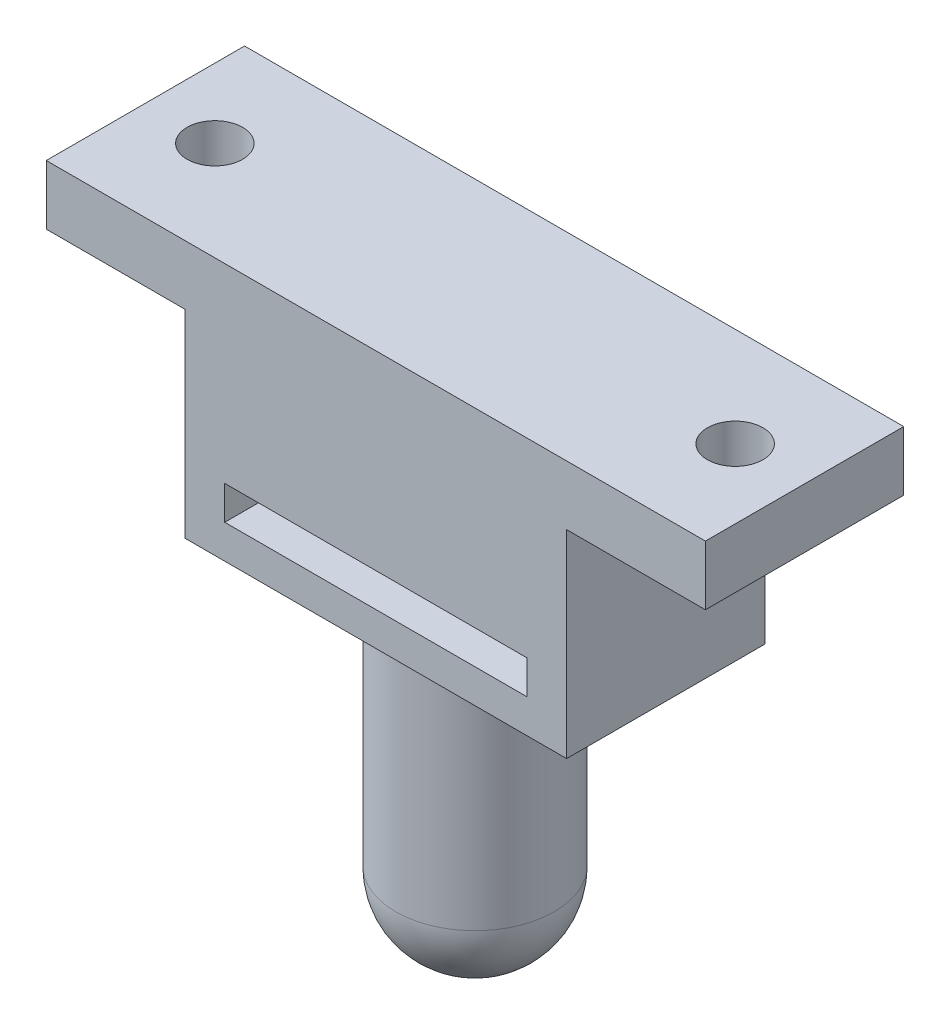
SolidWorks part; units mm, degrees
ref_plane "Front Plane" through (0, 0, 0) normal (0, 0, 1) x (1, 0, 0)
ref_plane "Top Plane" through (0, 0, 0) normal (0, 1, 0) x (1, 0, 0)
ref_plane "Right Plane" through (0, 0, 0) normal (1, 0, 0) x (0, 0, -1)
sketch "Sketch1" plane through (0, 0, 0) normal (0, 1, 0) x (1, 0, 0)
  line L1 (-9.62, -5) -> (9.62, -5)
  line L2 (-9.62, -5) -> (-9.62, 5)
  line L3 (-9.62, 5) -> (9.62, 5)
  line L4 (9.62, -5) -> (9.62, 5)
  line L5 (-9.62, -5) -> (9.62, 5) construction
  line L6 (-9.62, 5) -> (9.62, -5) construction
  line L7 (-9.62, 5) -> (-16.62, 5)
  line L8 (-9.62, 5) -> (-9.62, -5)
  line L9 (-9.62, -5) -> (-16.62, -5)
  line L10 (-16.62, 5) -> (-16.62, -5)
  line L11 (9.62, 5) -> (16.62, 5)
  line L12 (9.62, 5) -> (9.62, -5)
  line L13 (9.62, -5) -> (16.62, -5)
  line L14 (16.62, 5) -> (16.62, -5)
  point P0 (0, 0)
  dimension "D1" = 19.24
  dimension "D2" = 10
  dimension "D3" = 7
extrude "Boss-Extrude1" add sketch "Sketch1" against normal blind 3 contours L7 L10 L9 L2 | L14 L11 L4 L13 region at (-13.12, 0, 0) region at (13.12, 0, 0)
extrude "Boss-Extrude2" add sketch "Sketch1<4>" against normal blind 13 contours L1 L4 L3 L2 region at (0, 0, 0)
sketch "Sketch1<4>" plane through (0, 0, 0) normal (0, 1, 0) x (1, 0, 0) same geometry as "Sketch1"
sketch "Sketch2" plane through (0, 0, 5) normal (0, 0, 1) x (1, 0, 0)
  line L0 (0, -55) -> (0, 55) construction
  line L1 (-7.62, -11.3) -> (7.62, -11.3)
  line L2 (-7.62, -11.3) -> (-7.62, -9.6)
  line L3 (-7.62, -9.6) -> (7.62, -9.6)
  line L4 (7.62, -11.3) -> (7.62, -9.6)
  line L5 (-7.62, -11.3) -> (7.62, -9.6) construction
  line L6 (-7.62, -9.6) -> (7.62, -11.3) construction
  line L7 (55, 0) -> (-55, 0) construction
  point P0 (0, -10.45)
  dimension "D1" = 9.6
  dimension "D2" = 1.7
  dimension "D3" = 15.24
extrude "Cut-Extrude1" cut sketch "Sketch2" against normal blind 14
sketch "Sketch3" plane through (0, -13, 0) normal (0, -1, 0) x (1, 0, 0)
  circle A0 centre (0, 0) radius 4
  dimension "D1" = 8
extrude "Boss-Extrude3" add sketch "Sketch3" along normal blind 16
fillet "Fillet1" radius 4 1 edges at (0, -29, -4)
sketch "Sketch4" plane through (0, 0, 0) normal (0, 1, 0) x (1, 0, 0)
  line L0 (-7.15, 0) -> (7.15, 0) construction
  line L1 (-16.62, 5) -> (-16.62, -5) construction
  line L2 (16.62, 5) -> (16.62, -5) construction
  line L4 (-15.62, 1.4434) -> (-15.62, -1.4434)
  line L5 (-15.62, -1.4434) -> (-13.12, -2.8868)
  line L6 (-13.12, -2.8868) -> (-10.62, -1.4434)
  line L7 (-10.62, -1.4434) -> (-10.62, 1.4434)
  line L8 (-10.62, 1.4434) -> (-13.12, 2.8868)
  line L9 (-13.12, 2.8868) -> (-15.62, 1.4434)
  line L10 (10.62, 1.4434) -> (10.62, -1.4434)
  line L11 (10.62, -1.4434) -> (13.12, -2.8868)
  line L12 (13.12, -2.8868) -> (15.62, -1.4434)
  line L13 (15.62, -1.4434) -> (15.62, 1.4434)
  line L14 (15.62, 1.4434) -> (13.12, 2.8868)
  line L15 (13.12, 2.8868) -> (10.62, 1.4434)
  circle A0 centre (-13.12, 0) radius 1.4
  circle A1 centre (13.12, 0) radius 1.4
  circle A2 centre (-13.12, 0) radius 2.5 construction
  circle A3 centre (13.12, 0) radius 2.5 construction
  dimension "D1" = 2.8
  dimension "D2" = 2.8
  dimension "D3" = 3.5
  dimension "D4" = 3.5
  dimension "D5" = 5
  dimension "D6" = 5
extrude "Cut-Extrude2" cut sketch "Sketch4" against normal up to next contours A0 | A1 region at (-13.12, 0, 0) region at (13.12, 0, 0)
extrude "Cut-Extrude3" cut sketch "Sketch4<3>" against normal up to next from offset 2 offset against normal yes
sketch "Sketch4<3>" plane through (0, 0, 0) normal (0, 1, 0) x (1, 0, 0) same geometry as "Sketch4"
